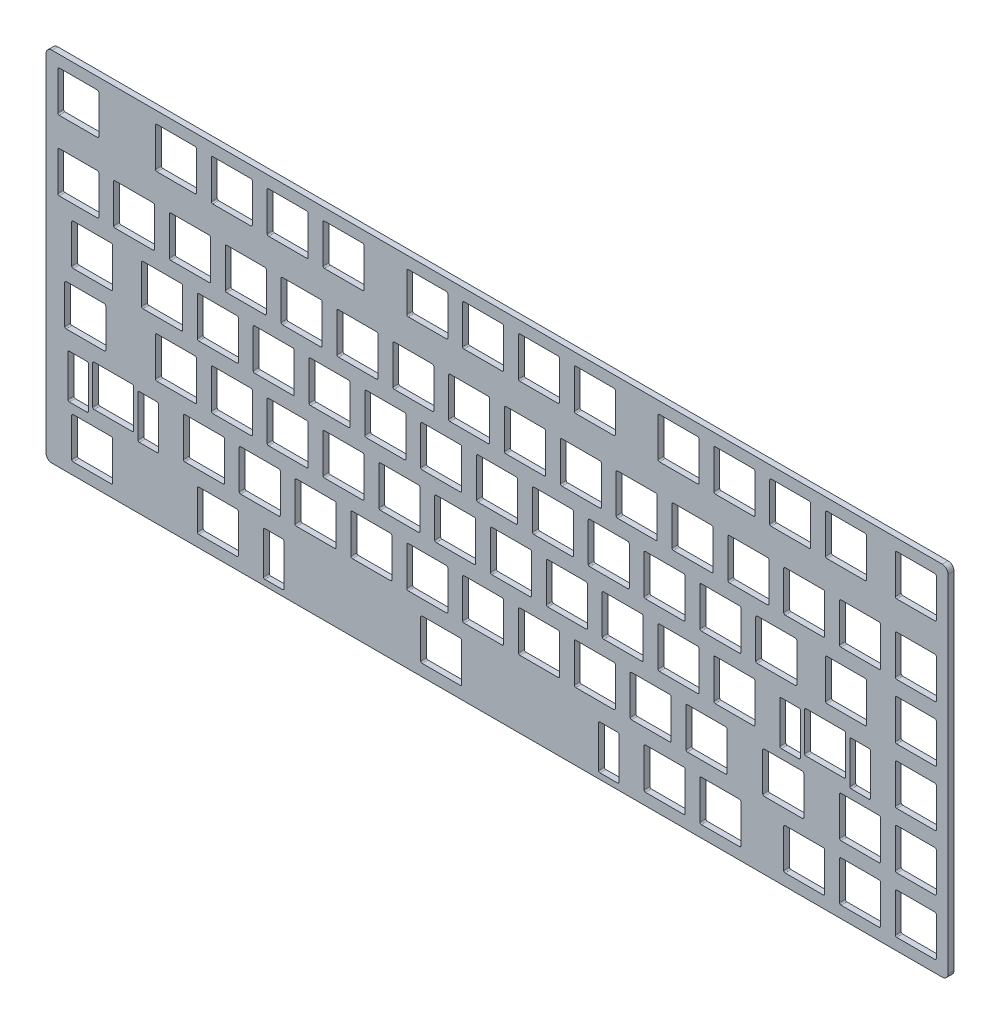
SolidWorks part; units mm, degrees
ref_plane "Front Plane" through (0, 0, 0) normal (0, 0, 1) x (1, 0, 0)
ref_plane "Top Plane" through (0, 0, 0) normal (0, 1, 0) x (1, 0, 0)
ref_plane "Right Plane" through (0, 0, 0) normal (1, 0, 0) x (0, 0, -1)
sketch "Base_Import_Plate" plane through (0, 0, 0) normal (0, 0, 1) x (1, 0, 0)
  line L0 (12.05, 126.0625) -> (26.05, 126.0625)
  line L1 (12.05, 112.0625) -> (26.05, 112.0625)
  line L2 (12.05, 126.0625) -> (12.05, 112.0625)
  line L3 (26.05, 126.0625) -> (26.05, 112.0625)
  line L4 (45.3875, 126.0625) -> (59.3875, 126.0625)
  line L5 (45.3875, 112.0625) -> (59.3875, 112.0625)
  line L6 (45.3875, 126.0625) -> (45.3875, 112.0625)
  line L7 (59.3875, 126.0625) -> (59.3875, 112.0625)
  line L8 (64.4375, 126.0625) -> (78.4375, 126.0625)
  line L9 (64.4375, 112.0625) -> (78.4375, 112.0625)
  line L10 (64.4375, 126.0625) -> (64.4375, 112.0625)
  line L11 (78.4375, 126.0625) -> (78.4375, 112.0625)
  line L12 (83.4875, 126.0625) -> (97.4875, 126.0625)
  line L13 (83.4875, 112.0625) -> (97.4875, 112.0625)
  line L14 (83.4875, 126.0625) -> (83.4875, 112.0625)
  line L15 (97.4875, 126.0625) -> (97.4875, 112.0625)
  line L16 (102.5375, 126.0625) -> (116.5375, 126.0625)
  line L17 (102.5375, 112.0625) -> (116.5375, 112.0625)
  line L18 (102.5375, 126.0625) -> (102.5375, 112.0625)
  line L19 (116.5375, 126.0625) -> (116.5375, 112.0625)
  line L20 (131.1125, 126.0625) -> (145.1125, 126.0625)
  line L21 (131.1125, 112.0625) -> (145.1125, 112.0625)
  line L22 (131.1125, 126.0625) -> (131.1125, 112.0625)
  line L23 (145.1125, 126.0625) -> (145.1125, 112.0625)
  line L24 (150.1625, 126.0625) -> (164.1625, 126.0625)
  line L25 (150.1625, 112.0625) -> (164.1625, 112.0625)
  line L26 (150.1625, 126.0625) -> (150.1625, 112.0625)
  line L27 (164.1625, 126.0625) -> (164.1625, 112.0625)
  line L28 (169.2125, 126.0625) -> (183.2125, 126.0625)
  line L29 (169.2125, 112.0625) -> (183.2125, 112.0625)
  line L30 (169.2125, 126.0625) -> (169.2125, 112.0625)
  line L31 (183.2125, 126.0625) -> (183.2125, 112.0625)
  line L32 (188.2625, 126.0625) -> (202.2625, 126.0625)
  line L33 (188.2625, 112.0625) -> (202.2625, 112.0625)
  line L34 (188.2625, 126.0625) -> (188.2625, 112.0625)
  line L35 (202.2625, 126.0625) -> (202.2625, 112.0625)
  line L36 (216.8375, 126.0625) -> (230.8375, 126.0625)
  line L37 (216.8375, 112.0625) -> (230.8375, 112.0625)
  line L38 (216.8375, 126.0625) -> (216.8375, 112.0625)
  line L39 (230.8375, 126.0625) -> (230.8375, 112.0625)
  line L40 (235.8875, 126.0625) -> (249.8875, 126.0625)
  line L41 (235.8875, 112.0625) -> (249.8875, 112.0625)
  line L42 (235.8875, 126.0625) -> (235.8875, 112.0625)
  line L43 (249.8875, 126.0625) -> (249.8875, 112.0625)
  line L44 (254.9375, 126.0625) -> (268.9375, 126.0625)
  line L45 (254.9375, 112.0625) -> (268.9375, 112.0625)
  line L46 (254.9375, 126.0625) -> (254.9375, 112.0625)
  line L47 (268.9375, 126.0625) -> (268.9375, 112.0625)
  line L48 (273.9875, 126.0625) -> (287.9875, 126.0625)
  line L49 (273.9875, 112.0625) -> (287.9875, 112.0625)
  line L50 (273.9875, 126.0625) -> (273.9875, 112.0625)
  line L51 (287.9875, 126.0625) -> (287.9875, 112.0625)
  line L52 (297.8, 126.0625) -> (311.8, 126.0625)
  line L53 (297.8, 112.0625) -> (311.8, 112.0625)
  line L54 (297.8, 126.0625) -> (297.8, 112.0625)
  line L55 (311.8, 126.0625) -> (311.8, 112.0625)
  line L56 (12.05, 102.25) -> (26.05, 102.25)
  line L57 (12.05, 88.25) -> (26.05, 88.25)
  line L58 (12.05, 102.25) -> (12.05, 88.25)
  line L59 (26.05, 102.25) -> (26.05, 88.25)
  line L60 (31.1, 102.25) -> (45.1, 102.25)
  line L61 (31.1, 88.25) -> (45.1, 88.25)
  line L62 (31.1, 102.25) -> (31.1, 88.25)
  line L63 (45.1, 102.25) -> (45.1, 88.25)
  line L64 (50.15, 102.25) -> (64.15, 102.25)
  line L65 (50.15, 88.25) -> (64.15, 88.25)
  line L66 (50.15, 102.25) -> (50.15, 88.25)
  line L67 (64.15, 102.25) -> (64.15, 88.25)
  line L68 (69.2, 102.25) -> (83.2, 102.25)
  line L69 (69.2, 88.25) -> (83.2, 88.25)
  line L70 (69.2, 102.25) -> (69.2, 88.25)
  line L71 (83.2, 102.25) -> (83.2, 88.25)
  line L72 (88.25, 102.25) -> (102.25, 102.25)
  line L73 (88.25, 88.25) -> (102.25, 88.25)
  line L74 (88.25, 102.25) -> (88.25, 88.25)
  line L75 (102.25, 102.25) -> (102.25, 88.25)
  line L76 (107.3, 102.25) -> (121.3, 102.25)
  line L77 (107.3, 88.25) -> (121.3, 88.25)
  line L78 (107.3, 102.25) -> (107.3, 88.25)
  line L79 (121.3, 102.25) -> (121.3, 88.25)
  line L80 (126.35, 102.25) -> (140.35, 102.25)
  line L81 (126.35, 88.25) -> (140.35, 88.25)
  line L82 (126.35, 102.25) -> (126.35, 88.25)
  line L83 (140.35, 102.25) -> (140.35, 88.25)
  line L84 (145.4, 102.25) -> (159.4, 102.25)
  line L85 (145.4, 88.25) -> (159.4, 88.25)
  line L86 (145.4, 102.25) -> (145.4, 88.25)
  line L87 (159.4, 102.25) -> (159.4, 88.25)
  line L88 (164.45, 102.25) -> (178.45, 102.25)
  line L89 (164.45, 88.25) -> (178.45, 88.25)
  line L90 (164.45, 102.25) -> (164.45, 88.25)
  line L91 (178.45, 102.25) -> (178.45, 88.25)
  line L92 (183.5, 102.25) -> (197.5, 102.25)
  line L93 (183.5, 88.25) -> (197.5, 88.25)
  line L94 (183.5, 102.25) -> (183.5, 88.25)
  line L95 (197.5, 102.25) -> (197.5, 88.25)
  line L96 (202.55, 102.25) -> (216.55, 102.25)
  line L97 (202.55, 88.25) -> (216.55, 88.25)
  line L98 (202.55, 102.25) -> (202.55, 88.25)
  line L99 (216.55, 102.25) -> (216.55, 88.25)
  line L100 (221.6, 102.25) -> (235.6, 102.25)
  line L101 (221.6, 88.25) -> (235.6, 88.25)
  line L102 (221.6, 102.25) -> (221.6, 88.25)
  line L103 (235.6, 102.25) -> (235.6, 88.25)
  line L104 (240.65, 102.25) -> (254.65, 102.25)
  line L105 (240.65, 88.25) -> (254.65, 88.25)
  line L106 (240.65, 102.25) -> (240.65, 88.25)
  line L107 (254.65, 102.25) -> (254.65, 88.25)
  line L108 (259.7, 102.25) -> (273.7, 102.25)
  line L109 (259.7, 88.25) -> (273.7, 88.25)
  line L110 (259.7, 102.25) -> (259.7, 88.25)
  line L111 (273.7, 102.25) -> (273.7, 88.25)
  line L112 (278.75, 102.25) -> (292.75, 102.25)
  line L113 (278.75, 88.25) -> (292.75, 88.25)
  line L114 (278.75, 102.25) -> (278.75, 88.25)
  line L115 (292.75, 102.25) -> (292.75, 88.25)
  line L116 (297.8, 102.25) -> (311.8, 102.25)
  line L117 (297.8, 88.25) -> (311.8, 88.25)
  line L118 (297.8, 102.25) -> (297.8, 88.25)
  line L119 (311.8, 102.25) -> (311.8, 88.25)
  line L120 (16.8125, 83.2) -> (30.8125, 83.2)
  line L121 (16.8125, 69.2) -> (30.8125, 69.2)
  line L122 (16.8125, 83.2) -> (16.8125, 69.2)
  line L123 (30.8125, 83.2) -> (30.8125, 69.2)
  line L124 (40.625, 83.2) -> (54.625, 83.2)
  line L125 (40.625, 69.2) -> (54.625, 69.2)
  line L126 (40.625, 83.2) -> (40.625, 69.2)
  line L127 (54.625, 83.2) -> (54.625, 69.2)
  line L128 (59.675, 83.2) -> (73.675, 83.2)
  line L129 (59.675, 69.2) -> (73.675, 69.2)
  line L130 (59.675, 83.2) -> (59.675, 69.2)
  line L131 (73.675, 83.2) -> (73.675, 69.2)
  line L132 (78.725, 83.2) -> (92.725, 83.2)
  line L133 (78.725, 69.2) -> (92.725, 69.2)
  line L134 (78.725, 83.2) -> (78.725, 69.2)
  line L135 (92.725, 83.2) -> (92.725, 69.2)
  line L136 (97.775, 83.2) -> (111.775, 83.2)
  line L137 (97.775, 69.2) -> (111.775, 69.2)
  line L138 (97.775, 83.2) -> (97.775, 69.2)
  line L139 (111.775, 83.2) -> (111.775, 69.2)
  line L140 (116.825, 83.2) -> (130.825, 83.2)
  line L141 (116.825, 69.2) -> (130.825, 69.2)
  line L142 (116.825, 83.2) -> (116.825, 69.2)
  line L143 (130.825, 83.2) -> (130.825, 69.2)
  line L144 (135.875, 83.2) -> (149.875, 83.2)
  line L145 (135.875, 69.2) -> (149.875, 69.2)
  line L146 (135.875, 83.2) -> (135.875, 69.2)
  line L147 (149.875, 83.2) -> (149.875, 69.2)
  line L148 (154.925, 83.2) -> (168.925, 83.2)
  line L149 (154.925, 69.2) -> (168.925, 69.2)
  line L150 (154.925, 83.2) -> (154.925, 69.2)
  line L151 (168.925, 83.2) -> (168.925, 69.2)
  line L152 (173.975, 83.2) -> (187.975, 83.2)
  line L153 (173.975, 69.2) -> (187.975, 69.2)
  line L154 (173.975, 83.2) -> (173.975, 69.2)
  line L155 (187.975, 83.2) -> (187.975, 69.2)
  line L156 (193.025, 83.2) -> (207.025, 83.2)
  line L157 (193.025, 69.2) -> (207.025, 69.2)
  line L158 (193.025, 83.2) -> (193.025, 69.2)
  line L159 (207.025, 83.2) -> (207.025, 69.2)
  line L160 (212.075, 83.2) -> (226.075, 83.2)
  line L161 (212.075, 69.2) -> (226.075, 69.2)
  line L162 (212.075, 83.2) -> (212.075, 69.2)
  line L163 (226.075, 83.2) -> (226.075, 69.2)
  line L164 (231.125, 83.2) -> (245.125, 83.2)
  line L165 (231.125, 69.2) -> (245.125, 69.2)
  line L166 (231.125, 83.2) -> (231.125, 69.2)
  line L167 (245.125, 83.2) -> (245.125, 69.2)
  line L168 (250.175, 83.2) -> (264.175, 83.2)
  line L169 (250.175, 69.2) -> (264.175, 69.2)
  line L170 (250.175, 83.2) -> (250.175, 69.2)
  line L171 (264.175, 83.2) -> (264.175, 69.2)
  line L172 (273.9875, 83.2) -> (287.9875, 83.2)
  line L173 (273.9875, 69.2) -> (287.9875, 69.2)
  line L174 (273.9875, 83.2) -> (273.9875, 69.2)
  line L175 (287.9875, 83.2) -> (287.9875, 69.2)
  line L176 (297.8, 83.2) -> (311.8, 83.2)
  line L177 (297.8, 69.2) -> (311.8, 69.2)
  line L178 (297.8, 83.2) -> (297.8, 69.2)
  line L179 (311.8, 83.2) -> (311.8, 69.2)
  line L180 (14.4312, 64.15) -> (28.4312, 64.15)
  line L181 (14.4312, 50.15) -> (28.4312, 50.15)
  line L182 (14.4312, 64.15) -> (14.4312, 50.15)
  line L183 (28.4312, 64.15) -> (28.4312, 50.15)
  line L184 (45.3875, 64.15) -> (59.3875, 64.15)
  line L185 (45.3875, 50.15) -> (59.3875, 50.15)
  line L186 (45.3875, 64.15) -> (45.3875, 50.15)
  line L187 (59.3875, 64.15) -> (59.3875, 50.15)
  line L188 (64.4375, 64.15) -> (78.4375, 64.15)
  line L189 (64.4375, 50.15) -> (78.4375, 50.15)
  line L190 (64.4375, 64.15) -> (64.4375, 50.15)
  line L191 (78.4375, 64.15) -> (78.4375, 50.15)
  line L192 (83.4875, 64.15) -> (97.4875, 64.15)
  line L193 (83.4875, 50.15) -> (97.4875, 50.15)
  line L194 (83.4875, 64.15) -> (83.4875, 50.15)
  line L195 (97.4875, 64.15) -> (97.4875, 50.15)
  line L196 (102.5375, 64.15) -> (116.5375, 64.15)
  line L197 (102.5375, 50.15) -> (116.5375, 50.15)
  line L198 (102.5375, 64.15) -> (102.5375, 50.15)
  line L199 (116.5375, 64.15) -> (116.5375, 50.15)
  line L200 (121.5875, 64.15) -> (135.5875, 64.15)
  line L201 (121.5875, 50.15) -> (135.5875, 50.15)
  line L202 (121.5875, 64.15) -> (121.5875, 50.15)
  line L203 (135.5875, 64.15) -> (135.5875, 50.15)
  line L204 (140.6375, 64.15) -> (154.6375, 64.15)
  line L205 (140.6375, 50.15) -> (154.6375, 50.15)
  line L206 (140.6375, 64.15) -> (140.6375, 50.15)
  line L207 (154.6375, 64.15) -> (154.6375, 50.15)
  line L208 (159.6875, 64.15) -> (173.6875, 64.15)
  line L209 (159.6875, 50.15) -> (173.6875, 50.15)
  line L210 (159.6875, 64.15) -> (159.6875, 50.15)
  line L211 (173.6875, 64.15) -> (173.6875, 50.15)
  line L212 (178.7375, 64.15) -> (192.7375, 64.15)
  line L213 (178.7375, 50.15) -> (192.7375, 50.15)
  line L214 (178.7375, 64.15) -> (178.7375, 50.15)
  line L215 (192.7375, 64.15) -> (192.7375, 50.15)
  line L216 (197.7875, 64.15) -> (211.7875, 64.15)
  line L217 (197.7875, 50.15) -> (211.7875, 50.15)
  line L218 (197.7875, 64.15) -> (197.7875, 50.15)
  line L219 (211.7875, 64.15) -> (211.7875, 50.15)
  line L220 (216.8375, 64.15) -> (230.8375, 64.15)
  line L221 (216.8375, 50.15) -> (230.8375, 50.15)
  line L222 (216.8375, 64.15) -> (216.8375, 50.15)
  line L223 (230.8375, 64.15) -> (230.8375, 50.15)
  line L224 (235.8875, 64.15) -> (249.8875, 64.15)
  line L225 (235.8875, 50.15) -> (249.8875, 50.15)
  line L226 (235.8875, 64.15) -> (235.8875, 50.15)
  line L227 (249.8875, 64.15) -> (249.8875, 50.15)
  line L228 (266.8437, 64.15) -> (280.8437, 64.15)
  line L229 (266.8437, 50.15) -> (280.8437, 50.15)
  line L230 (266.8437, 64.15) -> (266.8437, 50.15)
  line L231 (280.8437, 64.15) -> (280.8437, 50.15)
  line L232 (282.2817, 63.15) -> (289.2817, 63.15)
  line L233 (282.2817, 48.15) -> (289.2817, 48.15)
  line L234 (282.2817, 63.15) -> (282.2817, 48.15)
  line L235 (289.2817, 63.15) -> (289.2817, 48.15)
  line L236 (258.4057, 63.15) -> (265.4057, 63.15)
  line L237 (258.4057, 48.15) -> (265.4057, 48.15)
  line L238 (258.4057, 63.15) -> (258.4057, 48.15)
  line L239 (265.4057, 63.15) -> (265.4057, 48.15)
  line L240 (297.8, 64.15) -> (311.8, 64.15)
  line L241 (297.8, 50.15) -> (311.8, 50.15)
  line L242 (297.8, 64.15) -> (297.8, 50.15)
  line L243 (311.8, 64.15) -> (311.8, 50.15)
  line L244 (23.9562, 45.1) -> (37.9562, 45.1)
  line L245 (23.9562, 31.1) -> (37.9562, 31.1)
  line L246 (23.9562, 45.1) -> (23.9562, 31.1)
  line L247 (37.9562, 45.1) -> (37.9562, 31.1)
  line L248 (39.3942, 44.1) -> (46.3942, 44.1)
  line L249 (39.3942, 29.1) -> (46.3942, 29.1)
  line L250 (39.3942, 44.1) -> (39.3942, 29.1)
  line L251 (46.3942, 44.1) -> (46.3942, 29.1)
  line L252 (15.5182, 44.1) -> (22.5182, 44.1)
  line L253 (15.5182, 29.1) -> (22.5182, 29.1)
  line L254 (15.5182, 44.1) -> (15.5182, 29.1)
  line L255 (22.5182, 44.1) -> (22.5182, 29.1)
  line L256 (54.9125, 45.1) -> (68.9125, 45.1)
  line L257 (54.9125, 31.1) -> (68.9125, 31.1)
  line L258 (54.9125, 45.1) -> (54.9125, 31.1)
  line L259 (68.9125, 45.1) -> (68.9125, 31.1)
  line L260 (73.9625, 45.1) -> (87.9625, 45.1)
  line L261 (73.9625, 31.1) -> (87.9625, 31.1)
  line L262 (73.9625, 45.1) -> (73.9625, 31.1)
  line L263 (87.9625, 45.1) -> (87.9625, 31.1)
  line L264 (93.0125, 45.1) -> (107.0125, 45.1)
  line L265 (93.0125, 31.1) -> (107.0125, 31.1)
  line L266 (93.0125, 45.1) -> (93.0125, 31.1)
  line L267 (107.0125, 45.1) -> (107.0125, 31.1)
  line L268 (112.0625, 45.1) -> (126.0625, 45.1)
  line L269 (112.0625, 31.1) -> (126.0625, 31.1)
  line L270 (112.0625, 45.1) -> (112.0625, 31.1)
  line L271 (126.0625, 45.1) -> (126.0625, 31.1)
  line L272 (131.1125, 45.1) -> (145.1125, 45.1)
  line L273 (131.1125, 31.1) -> (145.1125, 31.1)
  line L274 (131.1125, 45.1) -> (131.1125, 31.1)
  line L275 (145.1125, 45.1) -> (145.1125, 31.1)
  line L276 (150.1625, 45.1) -> (164.1625, 45.1)
  line L277 (150.1625, 31.1) -> (164.1625, 31.1)
  line L278 (150.1625, 45.1) -> (150.1625, 31.1)
  line L279 (164.1625, 45.1) -> (164.1625, 31.1)
  line L280 (169.2125, 45.1) -> (183.2125, 45.1)
  line L281 (169.2125, 31.1) -> (183.2125, 31.1)
  line L282 (169.2125, 45.1) -> (169.2125, 31.1)
  line L283 (183.2125, 45.1) -> (183.2125, 31.1)
  line L284 (188.2625, 45.1) -> (202.2625, 45.1)
  line L285 (188.2625, 31.1) -> (202.2625, 31.1)
  line L286 (188.2625, 45.1) -> (188.2625, 31.1)
  line L287 (202.2625, 45.1) -> (202.2625, 31.1)
  line L288 (207.3125, 45.1) -> (221.3125, 45.1)
  line L289 (207.3125, 31.1) -> (221.3125, 31.1)
  line L290 (207.3125, 45.1) -> (207.3125, 31.1)
  line L291 (221.3125, 45.1) -> (221.3125, 31.1)
  line L292 (226.3625, 45.1) -> (240.3625, 45.1)
  line L293 (226.3625, 31.1) -> (240.3625, 31.1)
  line L294 (226.3625, 45.1) -> (226.3625, 31.1)
  line L295 (240.3625, 45.1) -> (240.3625, 31.1)
  line L296 (252.5562, 45.1) -> (266.5562, 45.1)
  line L297 (252.5562, 31.1) -> (266.5562, 31.1)
  line L298 (252.5562, 45.1) -> (252.5562, 31.1)
  line L299 (266.5562, 45.1) -> (266.5562, 31.1)
  line L300 (278.75, 45.1) -> (292.75, 45.1)
  line L301 (278.75, 31.1) -> (292.75, 31.1)
  line L302 (278.75, 45.1) -> (278.75, 31.1)
  line L303 (292.75, 45.1) -> (292.75, 31.1)
  line L304 (297.8, 45.1) -> (311.8, 45.1)
  line L305 (297.8, 31.1) -> (311.8, 31.1)
  line L306 (297.8, 45.1) -> (297.8, 31.1)
  line L307 (311.8, 45.1) -> (311.8, 31.1)
  line L308 (16.8125, 26.05) -> (30.8125, 26.05)
  line L309 (16.8125, 12.05) -> (30.8125, 12.05)
  line L310 (16.8125, 26.05) -> (16.8125, 12.05)
  line L311 (30.8125, 26.05) -> (30.8125, 12.05)
  line L312 (59.675, 26.05) -> (73.675, 26.05)
  line L313 (59.675, 12.05) -> (73.675, 12.05)
  line L314 (59.675, 26.05) -> (59.675, 12.05)
  line L315 (73.675, 26.05) -> (73.675, 12.05)
  line L316 (135.875, 26.05) -> (149.875, 26.05)
  line L317 (135.875, 12.05) -> (149.875, 12.05)
  line L318 (135.875, 26.05) -> (135.875, 12.05)
  line L319 (149.875, 26.05) -> (149.875, 12.05)
  line L320 (196.525, 25.05) -> (203.525, 25.05)
  line L321 (196.525, 10.05) -> (203.525, 10.05)
  line L322 (196.525, 25.05) -> (196.525, 10.05)
  line L323 (203.525, 25.05) -> (203.525, 10.05)
  line L324 (82.225, 25.05) -> (89.225, 25.05)
  line L325 (82.225, 10.05) -> (89.225, 10.05)
  line L326 (82.225, 25.05) -> (82.225, 10.05)
  line L327 (89.225, 25.05) -> (89.225, 10.05)
  line L328 (212.075, 26.05) -> (226.075, 26.05)
  line L329 (212.075, 12.05) -> (226.075, 12.05)
  line L330 (212.075, 26.05) -> (212.075, 12.05)
  line L331 (226.075, 26.05) -> (226.075, 12.05)
  line L332 (231.125, 26.05) -> (245.125, 26.05)
  line L333 (231.125, 12.05) -> (245.125, 12.05)
  line L334 (231.125, 26.05) -> (231.125, 12.05)
  line L335 (245.125, 26.05) -> (245.125, 12.05)
  line L336 (259.7, 26.05) -> (273.7, 26.05)
  line L337 (259.7, 12.05) -> (273.7, 12.05)
  line L338 (259.7, 26.05) -> (259.7, 12.05)
  line L339 (273.7, 26.05) -> (273.7, 12.05)
  line L340 (278.75, 26.05) -> (292.75, 26.05)
  line L341 (278.75, 12.05) -> (292.75, 12.05)
  line L342 (278.75, 26.05) -> (278.75, 12.05)
  line L343 (292.75, 26.05) -> (292.75, 12.05)
  line L344 (297.8, 26.05) -> (311.8, 26.05)
  line L345 (297.8, 12.05) -> (311.8, 12.05)
  line L346 (297.8, 26.05) -> (297.8, 12.05)
  line L347 (311.8, 26.05) -> (311.8, 12.05)
  circle A0 centre (19.05, 119.0625) radius 2
  circle A1 centre (19.05, 95.25) radius 2
  circle A2 centre (38.1, 95.25) radius 2
  circle A3 centre (52.3875, 119.0625) radius 2
  circle A4 centre (71.4375, 119.0625) radius 2
  circle A5 centre (90.4875, 119.0625) radius 2
  circle A6 centre (109.5375, 119.0625) radius 2
  circle A7 centre (138.1125, 119.0625) radius 2
  circle A8 centre (157.1625, 119.0625) radius 2
  circle A9 centre (176.2125, 119.0625) radius 2
  circle A10 centre (195.2625, 119.0625) radius 2
  circle A11 centre (223.8375, 119.0625) radius 2
  circle A12 centre (242.8875, 119.0625) radius 2
  circle A13 centre (261.9375, 119.0625) radius 2
  circle A14 centre (280.9875, 119.0625) radius 2
  circle A15 centre (304.8, 119.0625) radius 2
  circle A16 centre (57.15, 95.25) radius 2
  circle A17 centre (76.2, 95.25) radius 2
  circle A18 centre (95.25, 95.25) radius 2
  circle A19 centre (114.3, 95.25) radius 2
  circle A20 centre (133.35, 95.25) radius 2
  circle A21 centre (152.4, 95.25) radius 2
  circle A22 centre (171.45, 95.25) radius 2
  circle A23 centre (190.5, 95.25) radius 2
  circle A24 centre (209.55, 95.25) radius 2
  circle A25 centre (228.6, 95.25) radius 2
  circle A26 centre (247.65, 95.25) radius 2
  circle A27 centre (266.7, 95.25) radius 2
  circle A28 centre (285.75, 95.25) radius 2
  circle A29 centre (304.8, 95.25) radius 2
  circle A30 centre (304.8, 76.2) radius 2
  circle A31 centre (304.8, 57.15) radius 2
  circle A32 centre (304.8, 38.1) radius 2
  circle A33 centre (304.8, 19.05) radius 2
  circle A34 centre (285.75, 19.05) radius 2
  circle A35 centre (285.75, 38.1) radius 2
  circle A36 centre (273.8438, 57.15) radius 2
  circle A37 centre (280.9875, 76.2) radius 2
  circle A38 centre (257.175, 76.2) radius 2
  circle A39 centre (238.125, 76.2) radius 2
  circle A40 centre (219.075, 76.2) radius 2
  circle A41 centre (200.025, 76.2) radius 2
  circle A42 centre (180.975, 76.2) radius 2
  circle A43 centre (161.925, 76.2) radius 2
  circle A44 centre (142.875, 76.2) radius 2
  circle A45 centre (123.825, 76.2) radius 2
  circle A46 centre (104.775, 76.2) radius 2
  circle A47 centre (85.725, 76.2) radius 2
  circle A48 centre (66.675, 76.2) radius 2
  circle A49 centre (47.625, 76.2) radius 2
  circle A50 centre (23.8125, 76.2) radius 2
  circle A51 centre (21.4312, 57.15) radius 2
  circle A52 centre (30.9562, 38.1) radius 2
  circle A53 centre (52.3875, 57.15) radius 2
  circle A54 centre (71.4375, 57.15) radius 2
  circle A55 centre (90.4875, 57.15) radius 2
  circle A56 centre (61.9125, 38.1) radius 2
  circle A57 centre (66.675, 19.05) radius 2
  circle A58 centre (23.8125, 19.05) radius 2
  circle A59 centre (142.875, 19.05) radius 2
  circle A60 centre (80.9625, 38.1) radius 2
  circle A61 centre (100.0125, 38.1) radius 2
  circle A62 centre (119.0625, 38.1) radius 2
  circle A63 centre (109.5375, 57.15) radius 2
  circle A64 centre (128.5875, 57.15) radius 2
  circle A65 centre (147.6375, 57.15) radius 2
  circle A66 centre (138.1125, 38.1) radius 2
  circle A67 centre (157.1625, 38.1) radius 2
  circle A68 centre (166.6875, 57.15) radius 2
  circle A69 centre (185.7375, 57.15) radius 2
  circle A70 centre (204.7875, 57.15) radius 2
  circle A71 centre (223.8375, 57.15) radius 2
  circle A72 centre (242.8875, 57.15) radius 2
  circle A73 centre (259.5563, 38.1) radius 2
  circle A74 centre (266.7, 19.05) radius 2
  circle A75 centre (238.125, 19.05) radius 2
  circle A76 centre (219.075, 19.05) radius 2
  circle A77 centre (214.3125, 38.1) radius 2
  circle A78 centre (233.3625, 38.1) radius 2
  circle A79 centre (195.2625, 38.1) radius 2
  circle A80 centre (176.2125, 38.1) radius 2
  dimension "D1" = 19.05
  dimension "D2" = 95.25
sketch "Plate v1" plane through (0, 0, 0) normal (0, 0, 1) x (1, 0, 0)
  line L0 (187.975, 83.2) -> (187.975, 69.2) construction
  line L2 (311.8, 26.05) -> (311.8, 12.05) construction
  line L3 (297.8, 12.05) -> (311.8, 12.05) construction
  line L4 (297.8, 26.05) -> (297.8, 12.05) construction
  line L5 (297.8, 26.05) -> (311.8, 26.05) construction
  line L6 (311.8, 45.1) -> (311.8, 31.1) construction
  line L7 (297.8, 31.1) -> (311.8, 31.1) construction
  line L8 (297.8, 45.1) -> (297.8, 31.1) construction
  line L9 (297.8, 45.1) -> (311.8, 45.1) construction
  line L10 (311.8, 64.15) -> (311.8, 50.15) construction
  line L11 (297.8, 50.15) -> (311.8, 50.15) construction
  line L12 (297.8, 64.15) -> (297.8, 50.15) construction
  line L13 (297.8, 64.15) -> (311.8, 64.15) construction
  line L14 (297.8, 69.2) -> (311.8, 69.2) construction
  line L15 (297.8, 83.2) -> (297.8, 69.2) construction
  line L16 (297.8, 83.2) -> (311.8, 83.2) construction
  line L17 (297.8, 88.25) -> (311.8, 88.25) construction
  line L18 (311.8, 102.25) -> (311.8, 88.25) construction
  line L19 (297.8, 102.25) -> (311.8, 102.25) construction
  line L20 (297.8, 102.25) -> (297.8, 88.25) construction
  line L21 (297.8, 112.0625) -> (311.8, 112.0625) construction
  line L22 (311.8, 126.0625) -> (311.8, 112.0625) construction
  line L23 (297.8, 126.0625) -> (311.8, 126.0625) construction
  line L24 (297.8, 126.0625) -> (297.8, 112.0625) construction
  line L25 (287.9875, 126.0625) -> (287.9875, 112.0625) construction
  line L26 (273.9875, 126.0625) -> (287.9875, 126.0625) construction
  line L27 (273.9875, 126.0625) -> (273.9875, 112.0625) construction
  line L28 (273.9875, 112.0625) -> (287.9875, 112.0625) construction
  line L29 (278.75, 102.25) -> (292.75, 102.25) construction
  line L30 (292.75, 102.25) -> (292.75, 88.25) construction
  line L31 (278.75, 88.25) -> (292.75, 88.25) construction
  line L32 (278.75, 102.25) -> (278.75, 88.25) construction
  line L33 (259.7, 102.25) -> (273.7, 102.25) construction
  line L34 (273.7, 102.25) -> (273.7, 88.25) construction
  line L35 (259.7, 102.25) -> (259.7, 88.25) construction
  line L36 (259.7, 88.25) -> (273.7, 88.25) construction
  line L37 (273.9875, 83.2) -> (287.9875, 83.2) construction
  line L38 (287.9875, 83.2) -> (287.9875, 69.2) construction
  line L39 (273.9875, 69.2) -> (287.9875, 69.2) construction
  line L40 (273.9875, 83.2) -> (273.9875, 69.2) construction
  line L41 (282.2817, 63.15) -> (289.2817, 63.15) construction
  line L42 (289.2817, 63.15) -> (289.2817, 48.15) construction
  line L43 (282.2817, 48.15) -> (289.2817, 48.15) construction
  line L44 (282.2817, 63.15) -> (282.2817, 48.15) construction
  line L45 (280.8437, 64.15) -> (280.8437, 50.15) construction
  line L46 (266.8437, 64.15) -> (280.8437, 64.15) construction
  line L47 (266.8437, 50.15) -> (280.8437, 50.15) construction
  line L48 (266.8437, 64.15) -> (266.8437, 50.15) construction
  line L49 (265.4057, 63.15) -> (265.4057, 48.15) construction
  line L50 (258.4057, 63.15) -> (265.4057, 63.15) construction
  line L51 (258.4057, 63.15) -> (258.4057, 48.15) construction
  line L52 (258.4057, 48.15) -> (265.4057, 48.15) construction
  line L53 (252.5562, 45.1) -> (266.5562, 45.1) construction
  line L54 (266.5562, 45.1) -> (266.5562, 31.1) construction
  line L55 (252.5562, 31.1) -> (266.5562, 31.1) construction
  line L56 (252.5562, 45.1) -> (252.5562, 31.1) construction
  line L57 (278.75, 45.1) -> (292.75, 45.1) construction
  line L58 (292.75, 45.1) -> (292.75, 31.1) construction
  line L59 (278.75, 31.1) -> (292.75, 31.1) construction
  line L60 (278.75, 45.1) -> (278.75, 31.1) construction
  line L61 (292.75, 26.05) -> (292.75, 12.05) construction
  line L62 (278.75, 26.05) -> (292.75, 26.05) construction
  line L63 (278.75, 12.05) -> (292.75, 12.05) construction
  line L64 (278.75, 26.05) -> (278.75, 12.05) construction
  line L65 (273.7, 26.05) -> (273.7, 12.05) construction
  line L66 (259.7, 26.05) -> (273.7, 26.05) construction
  line L67 (259.7, 26.05) -> (259.7, 12.05) construction
  line L68 (259.7, 12.05) -> (273.7, 12.05) construction
  line L69 (245.125, 26.05) -> (245.125, 12.05) construction
  line L70 (231.125, 26.05) -> (245.125, 26.05) construction
  line L71 (231.125, 26.05) -> (231.125, 12.05) construction
  line L72 (231.125, 12.05) -> (245.125, 12.05) construction
  line L73 (226.075, 26.05) -> (226.075, 12.05) construction
  line L74 (212.075, 12.05) -> (226.075, 12.05) construction
  line L75 (212.075, 26.05) -> (226.075, 26.05) construction
  line L76 (212.075, 26.05) -> (212.075, 12.05) construction
  line L77 (207.3125, 31.1) -> (221.3125, 31.1) construction
  line L78 (221.3125, 45.1) -> (221.3125, 31.1) construction
  line L79 (207.3125, 45.1) -> (221.3125, 45.1) construction
  line L80 (207.3125, 45.1) -> (207.3125, 31.1) construction
  line L81 (226.3625, 45.1) -> (226.3625, 31.1) construction
  line L82 (226.3625, 45.1) -> (240.3625, 45.1) construction
  line L83 (240.3625, 45.1) -> (240.3625, 31.1) construction
  line L84 (226.3625, 31.1) -> (240.3625, 31.1) construction
  line L85 (235.8875, 50.15) -> (249.8875, 50.15) construction
  line L86 (249.8875, 64.15) -> (249.8875, 50.15) construction
  line L87 (235.8875, 64.15) -> (249.8875, 64.15) construction
  line L88 (235.8875, 64.15) -> (235.8875, 50.15) construction
  line L89 (250.175, 83.2) -> (250.175, 69.2) construction
  line L90 (250.175, 83.2) -> (264.175, 83.2) construction
  line L91 (264.175, 83.2) -> (264.175, 69.2) construction
  line L92 (250.175, 69.2) -> (264.175, 69.2) construction
  line L93 (254.65, 102.25) -> (254.65, 88.25) construction
  line L94 (240.65, 102.25) -> (254.65, 102.25) construction
  line L95 (240.65, 102.25) -> (240.65, 88.25) construction
  line L96 (240.65, 88.25) -> (254.65, 88.25) construction
  line L97 (231.125, 83.2) -> (245.125, 83.2) construction
  line L98 (245.125, 83.2) -> (245.125, 69.2) construction
  line L99 (231.125, 69.2) -> (245.125, 69.2) construction
  line L100 (231.125, 83.2) -> (231.125, 69.2) construction
  line L101 (235.6, 102.25) -> (235.6, 88.25) construction
  line L102 (221.6, 88.25) -> (235.6, 88.25) construction
  line L103 (221.6, 102.25) -> (235.6, 102.25) construction
  line L104 (221.6, 102.25) -> (221.6, 88.25) construction
  line L105 (254.9375, 112.0625) -> (268.9375, 112.0625) construction
  line L106 (268.9375, 126.0625) -> (268.9375, 112.0625) construction
  line L107 (254.9375, 126.0625) -> (268.9375, 126.0625) construction
  line L108 (254.9375, 126.0625) -> (254.9375, 112.0625) construction
  line L109 (249.8875, 126.0625) -> (249.8875, 112.0625) construction
  line L110 (235.8875, 112.0625) -> (249.8875, 112.0625) construction
  line L111 (235.8875, 126.0625) -> (249.8875, 126.0625) construction
  line L112 (235.8875, 126.0625) -> (235.8875, 112.0625) construction
  line L113 (230.8375, 126.0625) -> (230.8375, 112.0625) construction
  line L114 (216.8375, 112.0625) -> (230.8375, 112.0625) construction
  line L115 (216.8375, 126.0625) -> (230.8375, 126.0625) construction
  line L116 (216.8375, 126.0625) -> (216.8375, 112.0625) construction
  line L117 (188.2625, 112.0625) -> (202.2625, 112.0625) construction
  line L118 (202.2625, 126.0625) -> (202.2625, 112.0625) construction
  line L119 (188.2625, 126.0625) -> (202.2625, 126.0625) construction
  line L120 (188.2625, 126.0625) -> (188.2625, 112.0625) construction
  line L121 (183.2125, 126.0625) -> (183.2125, 112.0625) construction
  line L122 (169.2125, 126.0625) -> (183.2125, 126.0625) construction
  line L123 (150.1625, 126.0625) -> (164.1625, 126.0625) construction
  line L124 (131.1125, 126.0625) -> (145.1125, 126.0625) construction
  line L125 (102.5375, 126.0625) -> (116.5375, 126.0625) construction
  line L126 (83.4875, 126.0625) -> (97.4875, 126.0625) construction
  line L127 (64.4375, 126.0625) -> (78.4375, 126.0625) construction
  line L128 (45.3875, 126.0625) -> (59.3875, 126.0625) construction
  line L129 (12.05, 126.0625) -> (26.05, 126.0625) construction
  line L130 (12.05, 126.0625) -> (12.05, 112.0625) construction
  line L131 (12.05, 112.0625) -> (26.05, 112.0625) construction
  line L132 (26.05, 126.0625) -> (26.05, 112.0625) construction
  line L133 (45.3875, 126.0625) -> (45.3875, 112.0625) construction
  line L134 (45.3875, 112.0625) -> (59.3875, 112.0625) construction
  line L135 (59.3875, 126.0625) -> (59.3875, 112.0625) construction
  line L136 (64.4375, 126.0625) -> (64.4375, 112.0625) construction
  line L137 (64.4375, 112.0625) -> (78.4375, 112.0625) construction
  line L138 (78.4375, 126.0625) -> (78.4375, 112.0625) construction
  line L139 (83.4875, 112.0625) -> (97.4875, 112.0625) construction
  line L140 (97.4875, 126.0625) -> (97.4875, 112.0625) construction
  line L141 (83.4875, 126.0625) -> (83.4875, 112.0625) construction
  line L142 (102.5375, 126.0625) -> (102.5375, 112.0625) construction
  line L143 (116.5375, 126.0625) -> (116.5375, 112.0625) construction
  line L144 (102.5375, 112.0625) -> (116.5375, 112.0625) construction
  line L145 (131.1125, 126.0625) -> (131.1125, 112.0625) construction
  line L146 (131.1125, 112.0625) -> (145.1125, 112.0625) construction
  line L147 (145.1125, 126.0625) -> (145.1125, 112.0625) construction
  line L148 (150.1625, 126.0625) -> (150.1625, 112.0625) construction
  line L149 (164.1625, 126.0625) -> (164.1625, 112.0625) construction
  line L150 (169.2125, 126.0625) -> (169.2125, 112.0625) construction
  line L151 (169.2125, 112.0625) -> (183.2125, 112.0625) construction
  line L152 (150.1625, 112.0625) -> (164.1625, 112.0625) construction
  line L153 (202.55, 102.25) -> (216.55, 102.25) construction
  line L154 (216.55, 102.25) -> (216.55, 88.25) construction
  line L155 (202.55, 88.25) -> (216.55, 88.25) construction
  line L156 (202.55, 102.25) -> (202.55, 88.25) construction
  line L157 (183.5, 102.25) -> (197.5, 102.25) construction
  line L158 (197.5, 102.25) -> (197.5, 88.25) construction
  line L159 (183.5, 88.25) -> (197.5, 88.25) construction
  line L160 (193.025, 83.2) -> (207.025, 83.2) construction
  line L161 (212.075, 83.2) -> (226.075, 83.2) construction
  line L162 (226.075, 83.2) -> (226.075, 69.2) construction
  line L163 (212.075, 69.2) -> (226.075, 69.2) construction
  line L164 (230.8375, 64.15) -> (230.8375, 50.15) construction
  line L165 (216.8375, 64.15) -> (230.8375, 64.15) construction
  line L166 (216.8375, 64.15) -> (216.8375, 50.15) construction
  line L167 (216.8375, 50.15) -> (230.8375, 50.15) construction
  line L168 (202.2625, 45.1) -> (202.2625, 31.1) construction
  line L169 (203.525, 25.05) -> (203.525, 10.05) construction
  line L170 (196.525, 25.05) -> (203.525, 25.05) construction
  line L171 (196.525, 25.05) -> (196.525, 10.05) construction
  line L172 (196.525, 10.05) -> (203.525, 10.05) construction
  line L173 (188.2625, 31.1) -> (202.2625, 31.1) construction
  line L174 (188.2625, 45.1) -> (188.2625, 31.1) construction
  line L175 (188.2625, 45.1) -> (202.2625, 45.1) construction
  line L176 (197.7875, 50.15) -> (211.7875, 50.15) construction
  line L177 (197.7875, 64.15) -> (211.7875, 64.15) construction
  line L178 (211.7875, 64.15) -> (211.7875, 50.15) construction
  line L179 (212.075, 83.2) -> (212.075, 69.2) construction
  line L180 (207.025, 83.2) -> (207.025, 69.2) construction
  line L181 (193.025, 69.2) -> (207.025, 69.2) construction
  line L182 (197.7875, 64.15) -> (197.7875, 50.15) construction
  line L183 (193.025, 83.2) -> (193.025, 69.2) construction
  line L184 (173.975, 83.2) -> (187.975, 83.2) construction
  line L185 (173.975, 69.2) -> (187.975, 69.2) construction
  line L186 (178.7375, 64.15) -> (192.7375, 64.15) construction
  line L187 (192.7375, 64.15) -> (192.7375, 50.15) construction
  line L188 (178.7375, 64.15) -> (178.7375, 50.15) construction
  line L189 (16.8125, 26.05) -> (16.8125, 12.05) construction
  line L190 (16.8125, 12.05) -> (30.8125, 12.05) construction
  line L191 (30.8125, 26.05) -> (30.8125, 12.05) construction
  line L192 (16.8125, 26.05) -> (30.8125, 26.05) construction
  line L193 (22.5182, 44.1) -> (22.5182, 29.1) construction
  line L194 (15.5182, 29.1) -> (22.5182, 29.1) construction
  line L195 (15.5182, 44.1) -> (15.5182, 29.1) construction
  line L196 (15.5182, 44.1) -> (22.5182, 44.1) construction
  line L197 (23.9562, 45.1) -> (23.9562, 31.1) construction
  line L198 (23.9562, 31.1) -> (37.9562, 31.1) construction
  line L199 (23.9562, 45.1) -> (37.9562, 45.1) construction
  line L200 (37.9562, 45.1) -> (37.9562, 31.1) construction
  line L201 (39.3942, 44.1) -> (39.3942, 29.1) construction
  line L202 (39.3942, 29.1) -> (46.3942, 29.1) construction
  line L203 (46.3942, 44.1) -> (46.3942, 29.1) construction
  line L204 (39.3942, 44.1) -> (46.3942, 44.1) construction
  line L205 (45.3875, 64.15) -> (45.3875, 50.15) construction
  line L206 (28.4312, 64.15) -> (28.4312, 50.15) construction
  line L207 (14.4312, 50.15) -> (28.4312, 50.15) construction
  line L208 (14.4312, 64.15) -> (14.4312, 50.15) construction
  line L209 (14.4312, 64.15) -> (28.4312, 64.15) construction
  line L210 (16.8125, 83.2) -> (16.8125, 69.2) construction
  line L211 (16.8125, 69.2) -> (30.8125, 69.2) construction
  line L212 (30.8125, 83.2) -> (30.8125, 69.2) construction
  line L213 (16.8125, 83.2) -> (30.8125, 83.2) construction
  line L214 (12.05, 102.25) -> (12.05, 88.25) construction
  line L215 (12.05, 88.25) -> (26.05, 88.25) construction
  line L216 (26.05, 102.25) -> (26.05, 88.25) construction
  line L217 (12.05, 102.25) -> (26.05, 102.25) construction
  line L218 (31.1, 102.25) -> (31.1, 88.25) construction
  line L219 (31.1, 88.25) -> (45.1, 88.25) construction
  line L220 (45.1, 102.25) -> (45.1, 88.25) construction
  line L221 (31.1, 102.25) -> (45.1, 102.25) construction
  line L222 (50.15, 102.25) -> (50.15, 88.25) construction
  line L223 (50.15, 102.25) -> (64.15, 102.25) construction
  line L224 (64.15, 102.25) -> (64.15, 88.25) construction
  line L225 (50.15, 88.25) -> (64.15, 88.25) construction
  line L226 (40.625, 83.2) -> (40.625, 69.2) construction
  line L227 (54.625, 83.2) -> (54.625, 69.2) construction
  line L228 (40.625, 83.2) -> (54.625, 83.2) construction
  line L229 (40.625, 69.2) -> (54.625, 69.2) construction
  line L230 (45.3875, 64.15) -> (59.3875, 64.15) construction
  line L231 (45.3875, 50.15) -> (59.3875, 50.15) construction
  line L232 (59.3875, 64.15) -> (59.3875, 50.15) construction
  line L233 (54.9125, 45.1) -> (54.9125, 31.1) construction
  line L234 (54.9125, 45.1) -> (68.9125, 45.1) construction
  line L235 (68.9125, 45.1) -> (68.9125, 31.1) construction
  line L236 (54.9125, 31.1) -> (68.9125, 31.1) construction
  line L237 (59.675, 12.05) -> (73.675, 12.05) construction
  line L238 (59.675, 26.05) -> (59.675, 12.05) construction
  line L239 (59.675, 26.05) -> (73.675, 26.05) construction
  line L240 (73.675, 26.05) -> (73.675, 12.05) construction
  line L241 (82.225, 25.05) -> (82.225, 10.05) construction
  line L242 (82.225, 10.05) -> (89.225, 10.05) construction
  line L243 (89.225, 25.05) -> (89.225, 10.05) construction
  line L244 (82.225, 25.05) -> (89.225, 25.05) construction
  line L245 (73.9625, 31.1) -> (87.9625, 31.1) construction
  line L246 (73.9625, 45.1) -> (73.9625, 31.1) construction
  line L247 (73.9625, 45.1) -> (87.9625, 45.1) construction
  line L248 (64.4375, 64.15) -> (64.4375, 50.15) construction
  line L249 (64.4375, 50.15) -> (78.4375, 50.15) construction
  line L250 (78.4375, 64.15) -> (78.4375, 50.15) construction
  line L251 (64.4375, 64.15) -> (78.4375, 64.15) construction
  line L252 (59.675, 83.2) -> (59.675, 69.2) construction
  line L253 (59.675, 69.2) -> (73.675, 69.2) construction
  line L254 (73.675, 83.2) -> (73.675, 69.2) construction
  line L255 (59.675, 83.2) -> (73.675, 83.2) construction
  line L256 (78.725, 83.2) -> (78.725, 69.2) construction
  line L257 (78.725, 69.2) -> (92.725, 69.2) construction
  line L258 (83.4875, 64.15) -> (83.4875, 50.15) construction
  line L259 (87.9625, 45.1) -> (87.9625, 31.1) construction
  line L260 (93.0125, 45.1) -> (93.0125, 31.1) construction
  line L261 (83.4875, 50.15) -> (97.4875, 50.15) construction
  line L262 (97.775, 83.2) -> (97.775, 69.2) construction
  line L263 (92.725, 83.2) -> (92.725, 69.2) construction
  line L264 (97.4875, 64.15) -> (97.4875, 50.15) construction
  line L265 (83.4875, 64.15) -> (97.4875, 64.15) construction
  line L266 (102.5375, 64.15) -> (102.5375, 50.15) construction
  line L267 (97.775, 69.2) -> (111.775, 69.2) construction
  line L268 (111.775, 83.2) -> (111.775, 69.2) construction
  line L269 (116.825, 83.2) -> (116.825, 69.2) construction
  line L270 (116.825, 83.2) -> (130.825, 83.2) construction
  line L271 (97.775, 83.2) -> (111.775, 83.2) construction
  line L272 (78.725, 83.2) -> (92.725, 83.2) construction
  line L273 (69.2, 102.25) -> (69.2, 88.25) construction
  line L274 (69.2, 88.25) -> (83.2, 88.25) construction
  line L275 (83.2, 102.25) -> (83.2, 88.25) construction
  line L276 (69.2, 102.25) -> (83.2, 102.25) construction
  line L277 (88.25, 102.25) -> (88.25, 88.25) construction
  line L278 (88.25, 88.25) -> (102.25, 88.25) construction
  line L279 (88.25, 102.25) -> (102.25, 102.25) construction
  line L280 (102.25, 102.25) -> (102.25, 88.25) construction
  line L281 (107.3, 102.25) -> (107.3, 88.25) construction
  line L282 (107.3, 88.25) -> (121.3, 88.25) construction
  line L283 (107.3, 102.25) -> (121.3, 102.25) construction
  line L284 (121.3, 102.25) -> (121.3, 88.25) construction
  line L285 (126.35, 102.25) -> (126.35, 88.25) construction
  line L286 (126.35, 102.25) -> (140.35, 102.25) construction
  line L287 (140.35, 102.25) -> (140.35, 88.25) construction
  line L288 (126.35, 88.25) -> (140.35, 88.25) construction
  line L289 (130.825, 83.2) -> (130.825, 69.2) construction
  line L290 (116.825, 69.2) -> (130.825, 69.2) construction
  line L291 (112.0625, 45.1) -> (112.0625, 31.1) construction
  line L292 (102.5375, 64.15) -> (116.5375, 64.15) construction
  line L293 (116.5375, 64.15) -> (116.5375, 50.15) construction
  line L294 (102.5375, 50.15) -> (116.5375, 50.15) construction
  line L295 (93.0125, 31.1) -> (107.0125, 31.1) construction
  line L296 (93.0125, 45.1) -> (107.0125, 45.1) construction
  line L297 (107.0125, 45.1) -> (107.0125, 31.1) construction
  line L298 (112.0625, 31.1) -> (126.0625, 31.1) construction
  line L299 (112.0625, 45.1) -> (126.0625, 45.1) construction
  line L300 (126.0625, 45.1) -> (126.0625, 31.1) construction
  line L301 (121.5875, 64.15) -> (121.5875, 50.15) construction
  line L302 (121.5875, 50.15) -> (135.5875, 50.15) construction
  line L303 (135.5875, 64.15) -> (135.5875, 50.15) construction
  line L304 (135.875, 83.2) -> (135.875, 69.2) construction
  line L305 (121.5875, 64.15) -> (135.5875, 64.15) construction
  line L306 (140.6375, 64.15) -> (140.6375, 50.15) construction
  line L307 (140.6375, 64.15) -> (154.6375, 64.15) construction
  line L308 (135.875, 69.2) -> (149.875, 69.2) construction
  line L309 (149.875, 83.2) -> (149.875, 69.2) construction
  line L310 (154.925, 83.2) -> (154.925, 69.2) construction
  line L311 (135.875, 83.2) -> (149.875, 83.2) construction
  line L312 (145.4, 88.25) -> (159.4, 88.25) construction
  line L313 (145.4, 102.25) -> (145.4, 88.25) construction
  line L314 (145.4, 102.25) -> (159.4, 102.25) construction
  line L315 (159.4, 102.25) -> (159.4, 88.25) construction
  line L316 (183.2125, 45.1) -> (183.2125, 31.1) construction
  line L317 (169.2125, 45.1) -> (169.2125, 31.1) construction
  line L318 (154.6375, 64.15) -> (154.6375, 50.15) construction
  line L319 (140.6375, 50.15) -> (154.6375, 50.15) construction
  line L320 (131.1125, 45.1) -> (145.1125, 45.1) construction
  line L321 (131.1125, 45.1) -> (131.1125, 31.1) construction
  line L322 (135.875, 26.05) -> (135.875, 12.05) construction
  line L323 (135.875, 12.05) -> (149.875, 12.05) construction
  line L324 (149.875, 26.05) -> (149.875, 12.05) construction
  line L325 (135.875, 26.05) -> (149.875, 26.05) construction
  line L326 (131.1125, 31.1) -> (145.1125, 31.1) construction
  line L327 (145.1125, 45.1) -> (145.1125, 31.1) construction
  line L328 (150.1625, 45.1) -> (150.1625, 31.1) construction
  line L329 (150.1625, 45.1) -> (164.1625, 45.1) construction
  line L330 (164.1625, 45.1) -> (164.1625, 31.1) construction
  line L331 (150.1625, 31.1) -> (164.1625, 31.1) construction
  line L332 (169.2125, 31.1) -> (183.2125, 31.1) construction
  line L333 (169.2125, 45.1) -> (183.2125, 45.1) construction
  line L334 (159.6875, 64.15) -> (159.6875, 50.15) construction
  line L335 (173.6875, 64.15) -> (173.6875, 50.15) construction
  line L336 (159.6875, 50.15) -> (173.6875, 50.15) construction
  line L337 (159.6875, 64.15) -> (173.6875, 64.15) construction
  line L338 (154.925, 69.2) -> (168.925, 69.2) construction
  line L339 (168.925, 83.2) -> (168.925, 69.2) construction
  line L340 (154.925, 83.2) -> (168.925, 83.2) construction
  line L341 (164.45, 88.25) -> (178.45, 88.25) construction
  line L342 (164.45, 102.25) -> (164.45, 88.25) construction
  line L343 (164.45, 102.25) -> (178.45, 102.25) construction
  line L344 (183.5, 102.25) -> (183.5, 88.25) construction
  line L345 (178.45, 102.25) -> (178.45, 88.25) construction
  line L346 (173.975, 83.2) -> (173.975, 69.2) construction
  line L347 (16.8125, 26.05) -> (16.8125, 12.05)
  line L348 (16.8125, 12.05) -> (30.8125, 12.05)
  line L349 (30.8125, 26.05) -> (30.8125, 12.05)
  line L350 (16.8125, 26.05) -> (30.8125, 26.05)
  line L351 (22.5182, 44.1) -> (22.5182, 29.1)
  line L352 (15.5182, 29.1) -> (22.5182, 29.1)
  line L353 (15.5182, 44.1) -> (15.5182, 29.1)
  line L354 (15.5182, 44.1) -> (22.5182, 44.1)
  line L355 (23.9562, 45.1) -> (23.9562, 31.1)
  line L356 (23.9562, 31.1) -> (37.9562, 31.1)
  line L357 (23.9562, 45.1) -> (37.9562, 45.1)
  line L358 (37.9562, 45.1) -> (37.9562, 31.1)
  line L359 (39.3942, 44.1) -> (39.3942, 29.1)
  line L360 (39.3942, 29.1) -> (46.3942, 29.1)
  line L361 (46.3942, 44.1) -> (46.3942, 29.1)
  line L362 (39.3942, 44.1) -> (46.3942, 44.1)
  line L363 (45.3875, 64.15) -> (45.3875, 50.15)
  line L364 (28.4312, 64.15) -> (28.4312, 50.15)
  line L365 (14.4312, 50.15) -> (28.4312, 50.15)
  line L366 (14.4312, 64.15) -> (14.4312, 50.15)
  line L367 (14.4312, 64.15) -> (28.4312, 64.15)
  line L368 (16.8125, 83.2) -> (16.8125, 69.2)
  line L369 (16.8125, 69.2) -> (30.8125, 69.2)
  line L370 (30.8125, 83.2) -> (30.8125, 69.2)
  line L371 (16.8125, 83.2) -> (30.8125, 83.2)
  line L372 (12.05, 102.25) -> (12.05, 88.25)
  line L373 (12.05, 88.25) -> (26.05, 88.25)
  line L374 (26.05, 102.25) -> (26.05, 88.25)
  line L375 (12.05, 102.25) -> (26.05, 102.25)
  line L376 (31.1, 102.25) -> (31.1, 88.25)
  line L377 (31.1, 88.25) -> (45.1, 88.25)
  line L378 (45.1, 102.25) -> (45.1, 88.25)
  line L379 (31.1, 102.25) -> (45.1, 102.25)
  line L380 (50.15, 102.25) -> (50.15, 88.25)
  line L381 (50.15, 102.25) -> (64.15, 102.25)
  line L382 (64.15, 102.25) -> (64.15, 88.25)
  line L383 (50.15, 88.25) -> (64.15, 88.25)
  line L384 (40.625, 83.2) -> (40.625, 69.2)
  line L385 (54.625, 83.2) -> (54.625, 69.2)
  line L386 (40.625, 83.2) -> (54.625, 83.2)
  line L387 (40.625, 69.2) -> (54.625, 69.2)
  line L388 (45.3875, 64.15) -> (59.3875, 64.15)
  line L389 (45.3875, 50.15) -> (59.3875, 50.15)
  line L390 (59.3875, 64.15) -> (59.3875, 50.15)
  line L391 (54.9125, 45.1) -> (54.9125, 31.1)
  line L392 (54.9125, 45.1) -> (68.9125, 45.1)
  line L393 (68.9125, 45.1) -> (68.9125, 31.1)
  line L394 (54.9125, 31.1) -> (68.9125, 31.1)
  line L395 (59.675, 12.05) -> (73.675, 12.05)
  line L396 (59.675, 26.05) -> (59.675, 12.05)
  line L397 (59.675, 26.05) -> (73.675, 26.05)
  line L398 (73.675, 26.05) -> (73.675, 12.05)
  line L399 (82.225, 25.05) -> (82.225, 10.05)
  line L400 (82.225, 10.05) -> (89.225, 10.05)
  line L401 (89.225, 25.05) -> (89.225, 10.05)
  line L402 (82.225, 25.05) -> (89.225, 25.05)
  line L403 (73.9625, 31.1) -> (87.9625, 31.1)
  line L404 (73.9625, 45.1) -> (73.9625, 31.1)
  line L405 (73.9625, 45.1) -> (87.9625, 45.1)
  line L406 (64.4375, 64.15) -> (64.4375, 50.15)
  line L407 (64.4375, 50.15) -> (78.4375, 50.15)
  line L408 (78.4375, 64.15) -> (78.4375, 50.15)
  line L409 (64.4375, 64.15) -> (78.4375, 64.15)
  line L410 (59.675, 83.2) -> (59.675, 69.2)
  line L411 (59.675, 69.2) -> (73.675, 69.2)
  line L412 (73.675, 83.2) -> (73.675, 69.2)
  line L413 (59.675, 83.2) -> (73.675, 83.2)
  line L414 (78.725, 83.2) -> (78.725, 69.2)
  line L415 (78.725, 69.2) -> (92.725, 69.2)
  line L416 (83.4875, 64.15) -> (83.4875, 50.15)
  line L417 (87.9625, 45.1) -> (87.9625, 31.1)
  line L418 (93.0125, 45.1) -> (93.0125, 31.1)
  line L419 (83.4875, 50.15) -> (97.4875, 50.15)
  line L420 (97.775, 83.2) -> (97.775, 69.2)
  line L421 (92.725, 83.2) -> (92.725, 69.2)
  line L422 (97.4875, 64.15) -> (97.4875, 50.15)
  line L423 (83.4875, 64.15) -> (97.4875, 64.15)
  line L424 (102.5375, 64.15) -> (102.5375, 50.15)
  line L425 (97.775, 69.2) -> (111.775, 69.2)
  line L426 (111.775, 83.2) -> (111.775, 69.2)
  line L427 (116.825, 83.2) -> (116.825, 69.2)
  line L428 (116.825, 83.2) -> (130.825, 83.2)
  line L429 (97.775, 83.2) -> (111.775, 83.2)
  line L430 (78.725, 83.2) -> (92.725, 83.2)
  line L431 (69.2, 102.25) -> (69.2, 88.25)
  line L432 (69.2, 88.25) -> (83.2, 88.25)
  line L433 (83.2, 102.25) -> (83.2, 88.25)
  line L434 (69.2, 102.25) -> (83.2, 102.25)
  line L435 (88.25, 102.25) -> (88.25, 88.25)
  line L436 (88.25, 88.25) -> (102.25, 88.25)
  line L437 (88.25, 102.25) -> (102.25, 102.25)
  line L438 (102.25, 102.25) -> (102.25, 88.25)
  line L439 (107.3, 102.25) -> (107.3, 88.25)
  line L440 (107.3, 88.25) -> (121.3, 88.25)
  line L441 (107.3, 102.25) -> (121.3, 102.25)
  line L442 (121.3, 102.25) -> (121.3, 88.25)
  line L443 (126.35, 102.25) -> (126.35, 88.25)
  line L444 (126.35, 102.25) -> (140.35, 102.25)
  line L445 (140.35, 102.25) -> (140.35, 88.25)
  line L446 (126.35, 88.25) -> (140.35, 88.25)
  line L447 (130.825, 83.2) -> (130.825, 69.2)
  line L448 (116.825, 69.2) -> (130.825, 69.2)
  line L449 (112.0625, 45.1) -> (112.0625, 31.1)
  line L450 (102.5375, 64.15) -> (116.5375, 64.15)
  line L451 (116.5375, 64.15) -> (116.5375, 50.15)
  line L452 (102.5375, 50.15) -> (116.5375, 50.15)
  line L453 (93.0125, 31.1) -> (107.0125, 31.1)
  line L454 (93.0125, 45.1) -> (107.0125, 45.1)
  line L455 (107.0125, 45.1) -> (107.0125, 31.1)
  line L456 (112.0625, 31.1) -> (126.0625, 31.1)
  line L457 (112.0625, 45.1) -> (126.0625, 45.1)
  line L458 (126.0625, 45.1) -> (126.0625, 31.1)
  line L459 (121.5875, 64.15) -> (121.5875, 50.15)
  line L460 (121.5875, 50.15) -> (135.5875, 50.15)
  line L461 (135.5875, 64.15) -> (135.5875, 50.15)
  line L462 (135.875, 83.2) -> (135.875, 69.2)
  line L463 (121.5875, 64.15) -> (135.5875, 64.15)
  line L464 (140.6375, 64.15) -> (140.6375, 50.15)
  line L465 (140.6375, 64.15) -> (154.6375, 64.15)
  line L466 (135.875, 69.2) -> (149.875, 69.2)
  line L467 (149.875, 83.2) -> (149.875, 69.2)
  line L468 (154.925, 83.2) -> (154.925, 69.2)
  line L469 (135.875, 83.2) -> (149.875, 83.2)
  line L470 (145.4, 88.25) -> (159.4, 88.25)
  line L471 (145.4, 102.25) -> (145.4, 88.25)
  line L472 (145.4, 102.25) -> (159.4, 102.25)
  line L473 (159.4, 102.25) -> (159.4, 88.25)
  line L474 (183.2125, 45.1) -> (183.2125, 31.1)
  line L475 (169.2125, 45.1) -> (169.2125, 31.1)
  line L476 (154.6375, 64.15) -> (154.6375, 50.15)
  line L477 (140.6375, 50.15) -> (154.6375, 50.15)
  line L478 (131.1125, 45.1) -> (145.1125, 45.1)
  line L479 (131.1125, 45.1) -> (131.1125, 31.1)
  line L480 (135.875, 26.05) -> (135.875, 12.05)
  line L481 (135.875, 12.05) -> (149.875, 12.05)
  line L482 (149.875, 26.05) -> (149.875, 12.05)
  line L483 (135.875, 26.05) -> (149.875, 26.05)
  line L484 (131.1125, 31.1) -> (145.1125, 31.1)
  line L485 (145.1125, 45.1) -> (145.1125, 31.1)
  line L486 (150.1625, 45.1) -> (150.1625, 31.1)
  line L487 (150.1625, 45.1) -> (164.1625, 45.1)
  line L488 (164.1625, 45.1) -> (164.1625, 31.1)
  line L489 (150.1625, 31.1) -> (164.1625, 31.1)
  line L490 (169.2125, 31.1) -> (183.2125, 31.1)
  line L491 (169.2125, 45.1) -> (183.2125, 45.1)
  line L492 (159.6875, 64.15) -> (159.6875, 50.15)
  line L493 (173.6875, 64.15) -> (173.6875, 50.15)
  line L494 (159.6875, 50.15) -> (173.6875, 50.15)
  line L495 (159.6875, 64.15) -> (173.6875, 64.15)
  line L496 (154.925, 69.2) -> (168.925, 69.2)
  line L497 (168.925, 83.2) -> (168.925, 69.2)
  line L498 (154.925, 83.2) -> (168.925, 83.2)
  line L499 (164.45, 88.25) -> (178.45, 88.25)
  line L500 (164.45, 102.25) -> (164.45, 88.25)
  line L501 (164.45, 102.25) -> (178.45, 102.25)
  line L502 (183.5, 102.25) -> (183.5, 88.25)
  line L503 (178.45, 102.25) -> (178.45, 88.25)
  line L504 (173.975, 83.2) -> (173.975, 69.2)
  line L505 (178.7375, 64.15) -> (178.7375, 50.15)
  line L506 (192.7375, 64.15) -> (192.7375, 50.15)
  line L507 (178.7375, 64.15) -> (192.7375, 64.15)
  line L508 (173.975, 69.2) -> (187.975, 69.2)
  line L509 (187.975, 83.2) -> (187.975, 69.2)
  line L510 (173.975, 83.2) -> (187.975, 83.2)
  line L511 (193.025, 83.2) -> (193.025, 69.2)
  line L512 (197.7875, 64.15) -> (197.7875, 50.15)
  line L513 (193.025, 69.2) -> (207.025, 69.2)
  line L514 (207.025, 83.2) -> (207.025, 69.2)
  line L515 (212.075, 83.2) -> (212.075, 69.2)
  line L516 (211.7875, 64.15) -> (211.7875, 50.15)
  line L517 (197.7875, 64.15) -> (211.7875, 64.15)
  line L518 (197.7875, 50.15) -> (211.7875, 50.15)
  line L519 (188.2625, 45.1) -> (202.2625, 45.1)
  line L520 (188.2625, 45.1) -> (188.2625, 31.1)
  line L521 (188.2625, 31.1) -> (202.2625, 31.1)
  line L522 (196.525, 10.05) -> (203.525, 10.05)
  line L523 (196.525, 25.05) -> (196.525, 10.05)
  line L524 (196.525, 25.05) -> (203.525, 25.05)
  line L525 (203.525, 25.05) -> (203.525, 10.05)
  line L526 (202.2625, 45.1) -> (202.2625, 31.1)
  line L527 (216.8375, 50.15) -> (230.8375, 50.15)
  line L528 (216.8375, 64.15) -> (216.8375, 50.15)
  line L529 (216.8375, 64.15) -> (230.8375, 64.15)
  line L530 (230.8375, 64.15) -> (230.8375, 50.15)
  line L531 (212.075, 69.2) -> (226.075, 69.2)
  line L532 (226.075, 83.2) -> (226.075, 69.2)
  line L533 (212.075, 83.2) -> (226.075, 83.2)
  line L534 (193.025, 83.2) -> (207.025, 83.2)
  line L535 (183.5, 88.25) -> (197.5, 88.25)
  line L536 (197.5, 102.25) -> (197.5, 88.25)
  line L537 (183.5, 102.25) -> (197.5, 102.25)
  line L538 (202.55, 102.25) -> (202.55, 88.25)
  line L539 (202.55, 88.25) -> (216.55, 88.25)
  line L540 (216.55, 102.25) -> (216.55, 88.25)
  line L541 (202.55, 102.25) -> (216.55, 102.25)
  line L542 (150.1625, 112.0625) -> (164.1625, 112.0625)
  line L543 (169.2125, 112.0625) -> (183.2125, 112.0625)
  line L544 (169.2125, 126.0625) -> (169.2125, 112.0625)
  line L545 (164.1625, 126.0625) -> (164.1625, 112.0625)
  line L546 (150.1625, 126.0625) -> (150.1625, 112.0625)
  line L547 (145.1125, 126.0625) -> (145.1125, 112.0625)
  line L548 (131.1125, 112.0625) -> (145.1125, 112.0625)
  line L549 (131.1125, 126.0625) -> (131.1125, 112.0625)
  line L550 (102.5375, 112.0625) -> (116.5375, 112.0625)
  line L551 (116.5375, 126.0625) -> (116.5375, 112.0625)
  line L552 (102.5375, 126.0625) -> (102.5375, 112.0625)
  line L553 (83.4875, 126.0625) -> (83.4875, 112.0625)
  line L554 (97.4875, 126.0625) -> (97.4875, 112.0625)
  line L555 (83.4875, 112.0625) -> (97.4875, 112.0625)
  line L556 (78.4375, 126.0625) -> (78.4375, 112.0625)
  line L557 (64.4375, 112.0625) -> (78.4375, 112.0625)
  line L558 (64.4375, 126.0625) -> (64.4375, 112.0625)
  line L559 (59.3875, 126.0625) -> (59.3875, 112.0625)
  line L560 (45.3875, 112.0625) -> (59.3875, 112.0625)
  line L561 (45.3875, 126.0625) -> (45.3875, 112.0625)
  line L562 (26.05, 126.0625) -> (26.05, 112.0625)
  line L563 (12.05, 112.0625) -> (26.05, 112.0625)
  line L564 (12.05, 126.0625) -> (12.05, 112.0625)
  line L565 (12.05, 126.0625) -> (26.05, 126.0625)
  line L566 (45.3875, 126.0625) -> (59.3875, 126.0625)
  line L567 (64.4375, 126.0625) -> (78.4375, 126.0625)
  line L568 (83.4875, 126.0625) -> (97.4875, 126.0625)
  line L569 (102.5375, 126.0625) -> (116.5375, 126.0625)
  line L570 (131.1125, 126.0625) -> (145.1125, 126.0625)
  line L571 (150.1625, 126.0625) -> (164.1625, 126.0625)
  line L572 (169.2125, 126.0625) -> (183.2125, 126.0625)
  line L573 (183.2125, 126.0625) -> (183.2125, 112.0625)
  line L574 (188.2625, 126.0625) -> (188.2625, 112.0625)
  line L575 (188.2625, 126.0625) -> (202.2625, 126.0625)
  line L576 (202.2625, 126.0625) -> (202.2625, 112.0625)
  line L577 (188.2625, 112.0625) -> (202.2625, 112.0625)
  line L578 (216.8375, 126.0625) -> (216.8375, 112.0625)
  line L579 (216.8375, 126.0625) -> (230.8375, 126.0625)
  line L580 (216.8375, 112.0625) -> (230.8375, 112.0625)
  line L581 (230.8375, 126.0625) -> (230.8375, 112.0625)
  line L582 (235.8875, 126.0625) -> (235.8875, 112.0625)
  line L583 (235.8875, 126.0625) -> (249.8875, 126.0625)
  line L584 (235.8875, 112.0625) -> (249.8875, 112.0625)
  line L585 (249.8875, 126.0625) -> (249.8875, 112.0625)
  line L586 (254.9375, 126.0625) -> (254.9375, 112.0625)
  line L587 (254.9375, 126.0625) -> (268.9375, 126.0625)
  line L588 (268.9375, 126.0625) -> (268.9375, 112.0625)
  line L589 (254.9375, 112.0625) -> (268.9375, 112.0625)
  line L590 (221.6, 102.25) -> (221.6, 88.25)
  line L591 (221.6, 102.25) -> (235.6, 102.25)
  line L592 (221.6, 88.25) -> (235.6, 88.25)
  line L593 (235.6, 102.25) -> (235.6, 88.25)
  line L594 (231.125, 83.2) -> (231.125, 69.2)
  line L595 (231.125, 69.2) -> (245.125, 69.2)
  line L596 (245.125, 83.2) -> (245.125, 69.2)
  line L597 (231.125, 83.2) -> (245.125, 83.2)
  line L598 (240.65, 88.25) -> (254.65, 88.25)
  line L599 (240.65, 102.25) -> (240.65, 88.25)
  line L600 (240.65, 102.25) -> (254.65, 102.25)
  line L601 (254.65, 102.25) -> (254.65, 88.25)
  line L602 (250.175, 69.2) -> (264.175, 69.2)
  line L603 (264.175, 83.2) -> (264.175, 69.2)
  line L604 (250.175, 83.2) -> (264.175, 83.2)
  line L605 (250.175, 83.2) -> (250.175, 69.2)
  line L606 (235.8875, 64.15) -> (235.8875, 50.15)
  line L607 (235.8875, 64.15) -> (249.8875, 64.15)
  line L608 (249.8875, 64.15) -> (249.8875, 50.15)
  line L609 (235.8875, 50.15) -> (249.8875, 50.15)
  line L610 (226.3625, 31.1) -> (240.3625, 31.1)
  line L611 (240.3625, 45.1) -> (240.3625, 31.1)
  line L612 (226.3625, 45.1) -> (240.3625, 45.1)
  line L613 (226.3625, 45.1) -> (226.3625, 31.1)
  line L614 (207.3125, 45.1) -> (207.3125, 31.1)
  line L615 (207.3125, 45.1) -> (221.3125, 45.1)
  line L616 (221.3125, 45.1) -> (221.3125, 31.1)
  line L617 (207.3125, 31.1) -> (221.3125, 31.1)
  line L618 (212.075, 26.05) -> (212.075, 12.05)
  line L619 (212.075, 26.05) -> (226.075, 26.05)
  line L620 (212.075, 12.05) -> (226.075, 12.05)
  line L621 (226.075, 26.05) -> (226.075, 12.05)
  line L622 (231.125, 12.05) -> (245.125, 12.05)
  line L623 (231.125, 26.05) -> (231.125, 12.05)
  line L624 (231.125, 26.05) -> (245.125, 26.05)
  line L625 (245.125, 26.05) -> (245.125, 12.05)
  line L626 (259.7, 12.05) -> (273.7, 12.05)
  line L627 (259.7, 26.05) -> (259.7, 12.05)
  line L628 (259.7, 26.05) -> (273.7, 26.05)
  line L629 (273.7, 26.05) -> (273.7, 12.05)
  line L630 (278.75, 26.05) -> (278.75, 12.05)
  line L631 (278.75, 12.05) -> (292.75, 12.05)
  line L632 (278.75, 26.05) -> (292.75, 26.05)
  line L633 (292.75, 26.05) -> (292.75, 12.05)
  line L634 (278.75, 45.1) -> (278.75, 31.1)
  line L635 (278.75, 31.1) -> (292.75, 31.1)
  line L636 (292.75, 45.1) -> (292.75, 31.1)
  line L637 (278.75, 45.1) -> (292.75, 45.1)
  line L638 (252.5562, 45.1) -> (252.5562, 31.1)
  line L639 (252.5562, 31.1) -> (266.5562, 31.1)
  line L640 (266.5562, 45.1) -> (266.5562, 31.1)
  line L641 (252.5562, 45.1) -> (266.5562, 45.1)
  line L642 (258.4057, 48.15) -> (265.4057, 48.15)
  line L643 (258.4057, 63.15) -> (258.4057, 48.15)
  line L644 (258.4057, 63.15) -> (265.4057, 63.15)
  line L645 (265.4057, 63.15) -> (265.4057, 48.15)
  line L646 (266.8437, 64.15) -> (266.8437, 50.15)
  line L647 (266.8437, 50.15) -> (280.8437, 50.15)
  line L648 (266.8437, 64.15) -> (280.8437, 64.15)
  line L649 (280.8437, 64.15) -> (280.8437, 50.15)
  line L650 (282.2817, 63.15) -> (282.2817, 48.15)
  line L651 (282.2817, 48.15) -> (289.2817, 48.15)
  line L652 (289.2817, 63.15) -> (289.2817, 48.15)
  line L653 (282.2817, 63.15) -> (289.2817, 63.15)
  line L654 (273.9875, 83.2) -> (273.9875, 69.2)
  line L655 (273.9875, 69.2) -> (287.9875, 69.2)
  line L656 (287.9875, 83.2) -> (287.9875, 69.2)
  line L657 (273.9875, 83.2) -> (287.9875, 83.2)
  line L658 (259.7, 88.25) -> (273.7, 88.25)
  line L659 (259.7, 102.25) -> (259.7, 88.25)
  line L660 (273.7, 102.25) -> (273.7, 88.25)
  line L661 (259.7, 102.25) -> (273.7, 102.25)
  line L662 (278.75, 102.25) -> (278.75, 88.25)
  line L663 (278.75, 88.25) -> (292.75, 88.25)
  line L664 (292.75, 102.25) -> (292.75, 88.25)
  line L665 (278.75, 102.25) -> (292.75, 102.25)
  line L666 (273.9875, 112.0625) -> (287.9875, 112.0625)
  line L667 (273.9875, 126.0625) -> (273.9875, 112.0625)
  line L668 (273.9875, 126.0625) -> (287.9875, 126.0625)
  line L669 (287.9875, 126.0625) -> (287.9875, 112.0625)
  line L670 (297.8, 126.0625) -> (297.8, 112.0625)
  line L671 (297.8, 126.0625) -> (311.8, 126.0625)
  line L672 (311.8, 126.0625) -> (311.8, 112.0625)
  line L673 (297.8, 112.0625) -> (311.8, 112.0625)
  line L674 (297.8, 102.25) -> (297.8, 88.25)
  line L675 (297.8, 102.25) -> (311.8, 102.25)
  line L676 (311.8, 102.25) -> (311.8, 88.25)
  line L677 (297.8, 88.25) -> (311.8, 88.25)
  line L678 (297.8, 83.2) -> (311.8, 83.2)
  line L679 (297.8, 83.2) -> (297.8, 69.2)
  line L680 (297.8, 69.2) -> (311.8, 69.2)
  line L681 (297.8, 64.15) -> (311.8, 64.15)
  line L682 (297.8, 64.15) -> (297.8, 50.15)
  line L683 (297.8, 50.15) -> (311.8, 50.15)
  line L684 (311.8, 64.15) -> (311.8, 50.15)
  line L685 (297.8, 45.1) -> (311.8, 45.1)
  line L686 (297.8, 45.1) -> (297.8, 31.1)
  line L687 (297.8, 31.1) -> (311.8, 31.1)
  line L688 (311.8, 45.1) -> (311.8, 31.1)
  line L689 (297.8, 26.05) -> (311.8, 26.05)
  line L690 (297.8, 26.05) -> (297.8, 12.05)
  line L691 (297.8, 12.05) -> (311.8, 12.05)
  line L692 (311.8, 26.05) -> (311.8, 12.05)
  line L693 (178.7375, 50.15) -> (192.7375, 50.15)
  line L694 (311.8, 83.2) -> (311.8, 69.2)
  line L696 (8.05, 130.0625) -> (315.8, 130.0625)
  line L697 (8.05, 130.0625) -> (8.05, 8.05)
  line L698 (8.05, 8.05) -> (315.8, 8.05)
  line L699 (315.8, 130.0625) -> (315.8, 8.05)
  dimension "D1" = 4
  dimension "D2" = 4
  dimension "D3" = 4
  dimension "D4" = 4
extrude "Plate Thickness" add sketch "Plate v1" along normal mid plane 2
fillet "2mm outside edge fillet" radius 2 4 edges at (8.05, 130.0625, 0) (315.8, 8.05, 0) (8.05, 8.05, 0) (315.8, 130.0625, 0)
fillet "0.5 cutout fillet" radius 0.5 348 edges at (178.45, 88.25, 0) (178.45, 102.25, 0) (164.45, 102.25, 0) (164.45, 88.25, 0) (159.6875, 50.15, 0) (173.6875, 50.15, 0) (173.6875, 64.15, 0) (159.6875, 64.15, 0) (150.1625, 31.1, 0) (164.1625, 31.1, 0) (164.1625, 45.1, 0) (150.1625, 45.1, 0) (135.875, 12.05, 0) (149.875, 12.05, 0) (149.875, 26.05, 0) (135.875, 26.05, 0) (145.1125, 31.1, 0) (145.1125, 45.1, 0) (131.1125, 45.1, 0) (131.1125, 31.1, 0) (169.2125, 31.1, 0) (183.2125, 31.1, 0) (183.2125, 45.1, 0) (169.2125, 45.1, 0) (159.4, 88.25, 0) (159.4, 102.25, 0) (145.4, 102.25, 0) (145.4, 88.25, 0) (154.925, 69.2, 0) (168.925, 69.2, 0) (168.925, 83.2, 0) (154.925, 83.2, 0) (140.6375, 50.15, 0) (154.6375, 50.15, 0) (154.6375, 64.15, 0) (140.6375, 64.15, 0) (135.875, 69.2, 0) (149.875, 69.2, 0) (149.875, 83.2, 0) (135.875, 83.2, 0) (121.5875, 50.15, 0) (135.5875, 50.15, 0) (135.5875, 64.15, 0) (121.5875, 64.15, 0) (112.0625, 31.1, 0) (126.0625, 31.1, 0) (126.0625, 45.1, 0) (112.0625, 45.1, 0) (126.35, 88.25, 0) (140.35, 88.25, 0) (140.35, 102.25, 0) (126.35, 102.25, 0) (107.3, 88.25, 0) (121.3, 88.25, 0) (121.3, 102.25, 0) (107.3, 102.25, 0) (88.25, 88.25, 0) (102.25, 88.25, 0) (102.25, 102.25, 0) (88.25, 102.25, 0) (69.2, 88.25, 0) (83.2, 88.25, 0) (83.2, 102.25, 0) (69.2, 102.25, 0) (116.825, 69.2, 0) (130.825, 69.2, 0) (130.825, 83.2, 0) (116.825, 83.2, 0) (102.5375, 50.15, 0) (116.5375, 50.15, 0) (116.5375, 64.15, 0) (102.5375, 64.15, 0) (97.775, 69.2, 0) (111.775, 69.2, 0) (111.775, 83.2, 0) (97.775, 83.2, 0) (93.0125, 31.1, 0) (107.0125, 31.1, 0) (107.0125, 45.1, 0) (93.0125, 45.1, 0) (83.4875, 50.15, 0) (97.4875, 50.15, 0) (97.4875, 64.15, 0) (83.4875, 64.15, 0) (78.725, 69.2, 0) (92.725, 69.2, 0) (92.725, 83.2, 0) (78.725, 83.2, 0) (59.675, 69.2, 0) (73.675, 69.2, 0) (73.675, 83.2, 0) (59.675, 83.2, 0) (64.4375, 50.15, 0) (78.4375, 50.15, 0) (78.4375, 64.15, 0) (64.4375, 64.15, 0) (87.9625, 31.1, 0) (87.9625, 45.1, 0) (73.9625, 45.1, 0) (73.9625, 31.1, 0) (82.225, 10.05, 0) (89.225, 10.05, 0) (89.225, 25.05, 0) (82.225, 25.05, 0) (73.675, 12.05, 0) (73.675, 26.05, 0) (59.675, 26.05, 0) (59.675, 12.05, 0) (54.9125, 31.1, 0) (68.9125, 31.1, 0) (68.9125, 45.1, 0) (54.9125, 45.1, 0) (40.625, 69.2, 0) (54.625, 69.2, 0) (54.625, 83.2, 0) (40.625, 83.2, 0) (50.15, 88.25, 0) (64.15, 88.25, 0) (64.15, 102.25, 0) (50.15, 102.25, 0) (31.1, 88.25, 0) (45.1, 88.25, 0) (45.1, 102.25, 0) (31.1, 102.25, 0) (12.05, 88.25, 0) (26.05, 88.25, 0) (26.05, 102.25, 0) (12.05, 102.25, 0) (16.8125, 69.2, 0) (30.8125, 69.2, 0) (30.8125, 83.2, 0) (16.8125, 83.2, 0) (14.4312, 50.15, 0) (28.4312, 50.15, 0) (28.4312, 64.15, 0) (14.4312, 64.15, 0) (45.3875, 50.15, 0) (59.3875, 50.15, 0) (59.3875, 64.15, 0) (45.3875, 64.15, 0) (39.3942, 29.1, 0) (46.3942, 29.1, 0) (46.3942, 44.1, 0) (39.3942, 44.1, 0) (23.9562, 31.1, 0) (37.9562, 31.1, 0) (37.9562, 45.1, 0) (23.9562, 45.1, 0) (15.5182, 29.1, 0) (22.5182, 29.1, 0) (22.5182, 44.1, 0) (15.5182, 44.1, 0) (16.8125, 12.05, 0) (30.8125, 12.05, 0) (30.8125, 26.05, 0) (16.8125, 26.05, 0) (178.7375, 50.15, 0) (192.7375, 50.15, 0) (192.7375, 64.15, 0) (178.7375, 64.15, 0) (193.025, 69.2, 0) (207.025, 69.2, 0) (207.025, 83.2, 0) (193.025, 83.2, 0) (197.7875, 50.15, 0) (211.7875, 50.15, 0) (211.7875, 64.15, 0) (197.7875, 64.15, 0) (188.2625, 45.1, 0) (188.2625, 31.1, 0) (202.2625, 31.1, 0) (202.2625, 45.1, 0) (196.525, 25.05, 0) (196.525, 10.05, 0) (203.525, 10.05, 0) (203.525, 25.05, 0) (216.8375, 64.15, 0) (216.8375, 50.15, 0) (230.8375, 50.15, 0) (230.8375, 64.15, 0) (212.075, 69.2, 0) (226.075, 69.2, 0) (226.075, 83.2, 0) (212.075, 83.2, 0) (183.5, 88.25, 0) (197.5, 88.25, 0) (197.5, 102.25, 0) (183.5, 102.25, 0) (202.55, 88.25, 0) (216.55, 88.25, 0) (216.55, 102.25, 0) (202.55, 102.25, 0) (150.1625, 112.0625, 0) (164.1625, 112.0625, 0) (164.1625, 126.0625, 0) (150.1625, 126.0625, 0) (131.1125, 112.0625, 0) (145.1125, 112.0625, 0) (145.1125, 126.0625, 0) (131.1125, 126.0625, 0) (102.5375, 112.0625, 0) (116.5375, 112.0625, 0) (116.5375, 126.0625, 0) (102.5375, 126.0625, 0) (83.4875, 112.0625, 0) (97.4875, 112.0625, 0) (97.4875, 126.0625, 0) (83.4875, 126.0625, 0) (64.4375, 112.0625, 0) (78.4375, 112.0625, 0) (78.4375, 126.0625, 0) (64.4375, 126.0625, 0) (45.3875, 112.0625, 0) (59.3875, 112.0625, 0) (59.3875, 126.0625, 0) (45.3875, 126.0625, 0) (12.05, 112.0625, 0) (26.05, 112.0625, 0) (26.05, 126.0625, 0) (12.05, 126.0625, 0) (169.2125, 126.0625, 0) (169.2125, 112.0625, 0) (183.2125, 112.0625, 0) (183.2125, 126.0625, 0) (202.2625, 126.0625, 0) (188.2625, 126.0625, 0) (188.2625, 112.0625, 0) (202.2625, 112.0625, 0) (216.8375, 126.0625, 0) (216.8375, 112.0625, 0) (230.8375, 112.0625, 0) (230.8375, 126.0625, 0) (235.8875, 126.0625, 0) (235.8875, 112.0625, 0) (249.8875, 112.0625, 0) (249.8875, 126.0625, 0) (268.9375, 126.0625, 0) (254.9375, 126.0625, 0) (254.9375, 112.0625, 0) (268.9375, 112.0625, 0) (221.6, 102.25, 0) (221.6, 88.25, 0) (235.6, 88.25, 0) (235.6, 102.25, 0) (231.125, 69.2, 0) (245.125, 69.2, 0) (245.125, 83.2, 0) (231.125, 83.2, 0) (240.65, 102.25, 0) (240.65, 88.25, 0) (254.65, 88.25, 0) (254.65, 102.25, 0) (264.175, 69.2, 0) (264.175, 83.2, 0) (250.175, 83.2, 0) (250.175, 69.2, 0) (249.8875, 64.15, 0) (235.8875, 64.15, 0) (235.8875, 50.15, 0) (249.8875, 50.15, 0) (240.3625, 31.1, 0) (240.3625, 45.1, 0) (226.3625, 45.1, 0) (226.3625, 31.1, 0) (221.3125, 45.1, 0) (207.3125, 45.1, 0) (207.3125, 31.1, 0) (221.3125, 31.1, 0) (212.075, 26.05, 0) (212.075, 12.05, 0) (226.075, 12.05, 0) (226.075, 26.05, 0) (231.125, 26.05, 0) (231.125, 12.05, 0) (245.125, 12.05, 0) (245.125, 26.05, 0) (259.7, 26.05, 0) (259.7, 12.05, 0) (273.7, 12.05, 0) (273.7, 26.05, 0) (278.75, 26.05, 0) (278.75, 12.05, 0) (292.75, 12.05, 0) (292.75, 26.05, 0) (278.75, 31.1, 0) (292.75, 31.1, 0) (292.75, 45.1, 0) (278.75, 45.1, 0) (252.5562, 31.1, 0) (266.5562, 31.1, 0) (266.5562, 45.1, 0) (252.5562, 45.1, 0) (258.4057, 63.15, 0) (258.4057, 48.15, 0) (265.4057, 48.15, 0) (265.4057, 63.15, 0) (266.8437, 64.15, 0) (266.8437, 50.15, 0) (280.8437, 50.15, 0) (280.8437, 64.15, 0) (282.2817, 48.15, 0) (289.2817, 48.15, 0) (289.2817, 63.15, 0) (282.2817, 63.15, 0) (273.9875, 69.2, 0) (287.9875, 69.2, 0) (287.9875, 83.2, 0) (273.9875, 83.2, 0) (259.7, 88.25, 0) (273.7, 88.25, 0) (273.7, 102.25, 0) (259.7, 102.25, 0) (278.75, 88.25, 0) (292.75, 88.25, 0) (292.75, 102.25, 0) (278.75, 102.25, 0) (273.9875, 126.0625, 0) (273.9875, 112.0625, 0) (287.9875, 112.0625, 0) (287.9875, 126.0625, 0) (297.8, 126.0625, 0) (297.8, 112.0625, 0) (311.8, 112.0625, 0) (311.8, 102.25, 0) (297.8, 102.25, 0) (297.8, 88.25, 0) (311.8, 88.25, 0) (297.8, 83.2, 0) (297.8, 69.2, 0) (311.8, 69.2, 0) (311.8, 83.2, 0) (297.8, 64.15, 0) (297.8, 50.15, 0) (311.8, 50.15, 0) (311.8, 64.15, 0) (297.8, 45.1, 0) (297.8, 31.1, 0) (311.8, 31.1, 0) (311.8, 45.1, 0) (297.8, 26.05, 0) (297.8, 12.05, 0) (311.8, 12.05, 0) (311.8, 26.05, 0) (173.975, 69.2, 0) (187.975, 69.2, 0) (187.975, 83.2, 0) (173.975, 83.2, 0) (311.8, 126.0625, 0)
